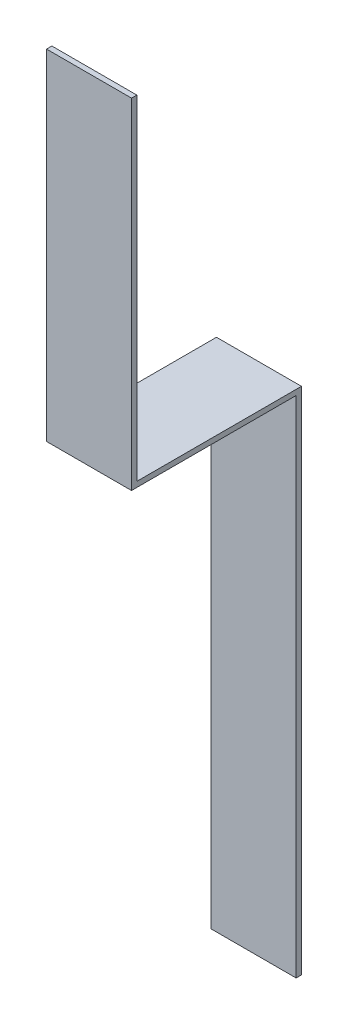
SolidWorks part; units mm, degrees
ref_plane "Front Plane" through (0, 0, 0) normal (0, 0, 1) x (1, 0, 0)
ref_plane "Top Plane" through (0, 0, 0) normal (0, 1, 0) x (1, 0, 0)
ref_plane "Right Plane" through (0, 0, 0) normal (1, 0, 0) x (0, 0, -1)
sketch "Sketch3" plane through (0, 0, 0) normal (1, 0, 0) x (0, 0, -1)
  line L0 (0, 0) -> (0, -101.6)
  line L1 (0, -101.6) -> (49.2125, -101.6)
  line L2 (49.2125, -101.6) -> (49.2125, -252.4125)
  line L3 (0, 0) -> (1.5875, 0)
  line L4 (1.5875, 0) -> (1.5875, -100.0125)
  line L5 (1.5875, -100.0125) -> (50.8, -100.0125)
  line L6 (50.8, -100.0125) -> (50.8, -252.4125)
  line L7 (50.8, -252.4125) -> (49.2125, -252.4125)
  dimension "D1" = 101.6
  dimension "D2" = 152.4
  dimension "D3" = 1.5875
  dimension "D4" = 50.8
  dimension "D5" = 1.5875
  dimension "D6" = 1.5875
extrude "Boss-Extrude1" add sketch "Sketch3" against normal blind 25.4 contours L2 L7 L6 L5 L4 L3 L0 L1
